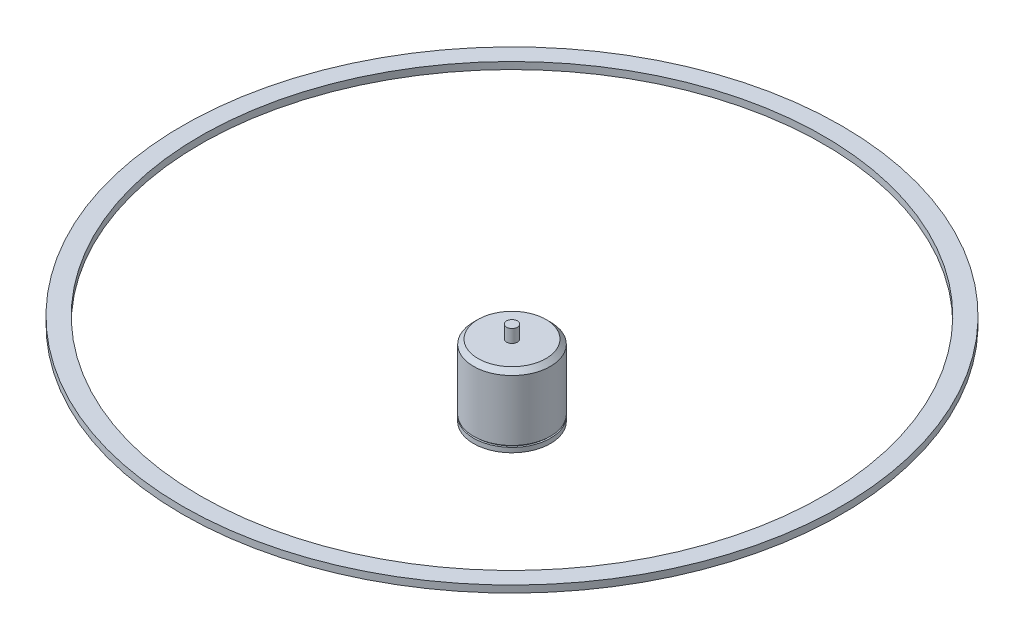
SolidWorks part; units mm, degrees
ref_plane "Front Plane" through (0, 0, 0) normal (0, 0, 1) x (1, 0, 0)
ref_plane "Top Plane" through (0, 0, 0) normal (0, 1, 0) x (1, 0, 0)
ref_plane "Right Plane" through (0, 0, 0) normal (1, 0, 0) x (0, 0, -1)
sketch "Sketch1" plane through (0, 0, 0) normal (0, 0, 1) x (1, 0, 0)
  line L0 (0, 0) -> (14, 0)
  line L1 (14, 0) -> (14, 1.7128)
  line L2 (12.3622, 26) -> (1.9951, 26)
  line L3 (14, 24.3622) -> (12.3622, 26)
  line L4 (14, 1.7128) -> (13.3774, 1.7128)
  line L5 (13.3774, 1.7128) -> (13.3774, 2.3033)
  line L6 (13.3774, 2.3033) -> (14, 2.3033)
  line L7 (14, 2.3033) -> (14, 24.3622)
  line L8 (1.9951, 26) -> (1.9951, 30.7205)
  line L9 (1.9951, 30.7205) -> (0, 30.7205)
  line L10 (0, 30.7205) -> (0, 0)
  dimension "D1" = 14
revolve "Revolve1" add sketch "Sketch1" angle 360 about L10
ref_axis "Axis1" through (0, 26, 0) along (0, 1, 0)
sketch "Sketch2" plane through (0, 30.7205, 0) normal (0, 1, 0) x (1, 0, 0)
  circle A0 centre (0, 0) radius 120.015
  circle A1 centre (0, 0) radius 113.5033
  dimension "D1" = 240.03
extrude "Boss-Extrude1" add sketch "Sketch2" along normal blind 2.54 contours A0 A1 region at (-116.6205, 30.7205, 0)
